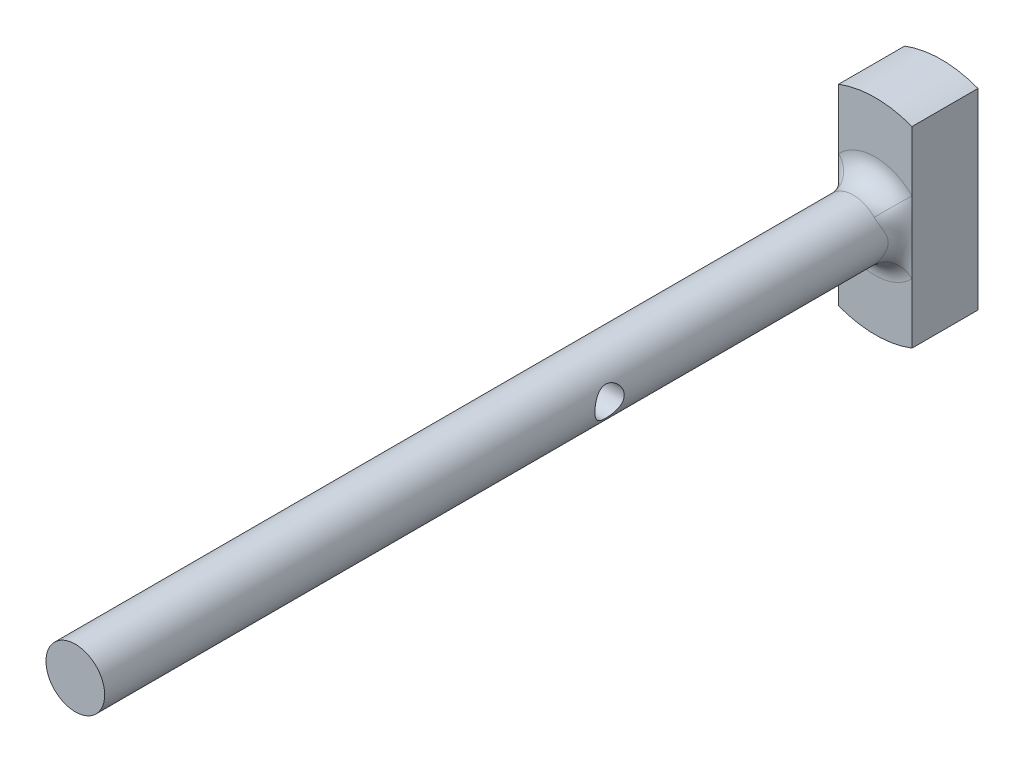
SolidWorks part; units mm, degrees
ref_plane "Front Plane" through (0, 0, 0) normal (0, 0, 1) x (1, 0, 0)
ref_plane "Top Plane" through (0, 0, 0) normal (0, 1, 0) x (1, 0, 0)
ref_plane "Right Plane" through (0, 0, 0) normal (1, 0, 0) x (0, 0, -1)
sketch "Sketch1" plane through (0, 0, 0) normal (0, 0, 1) x (1, 0, 0)
  line L0 (-2.5, -6.5383) -> (-2.5, 6.5383)
  line L1 (2.5, 6.5383) -> (2.5, -6.5383)
  arc A0 (-2.5, -6.5383) -> (2.5, -6.5383) centre (0, 0) ccw
  arc A1 (2.5, 6.5383) -> (-2.5, 6.5383) centre (0, 0) ccw
  dimension "D1" = 14
  dimension "D2" = 5
  dimension "D3" = 2.5
extrude "Boss-Extrude1" add sketch "Sketch1" along normal blind 4.5
sketch "Sketch2" plane through (0, 0, 4.5) normal (0, 0, 1) x (1, 0, 0)
  circle A0 centre (0, 0) radius 2
  dimension "D1" = 4
extrude "Boss-Extrude2" add sketch "Sketch2" along normal blind 54.5
fillet "Fillet1" radius 1.5 1 edges at (2, 0, 4.5)
sketch "Sketch3" plane through (0, 0, 0) normal (1, 0, 0) x (0, 0, -1)
  line L0 (-59, 2) -> (-59, -2) construction
  line L1 (-59, -2) -> (-6, -2) construction
  circle A0 centre (-24.6, 0) radius 1
  dimension "D1" = 2
  dimension "D2" = 34.4
  dimension "D3" = 2
extrude "Cut-Extrude1" cut sketch "Sketch3" along normal blind 5 from offset 2.5 offset against normal yes
